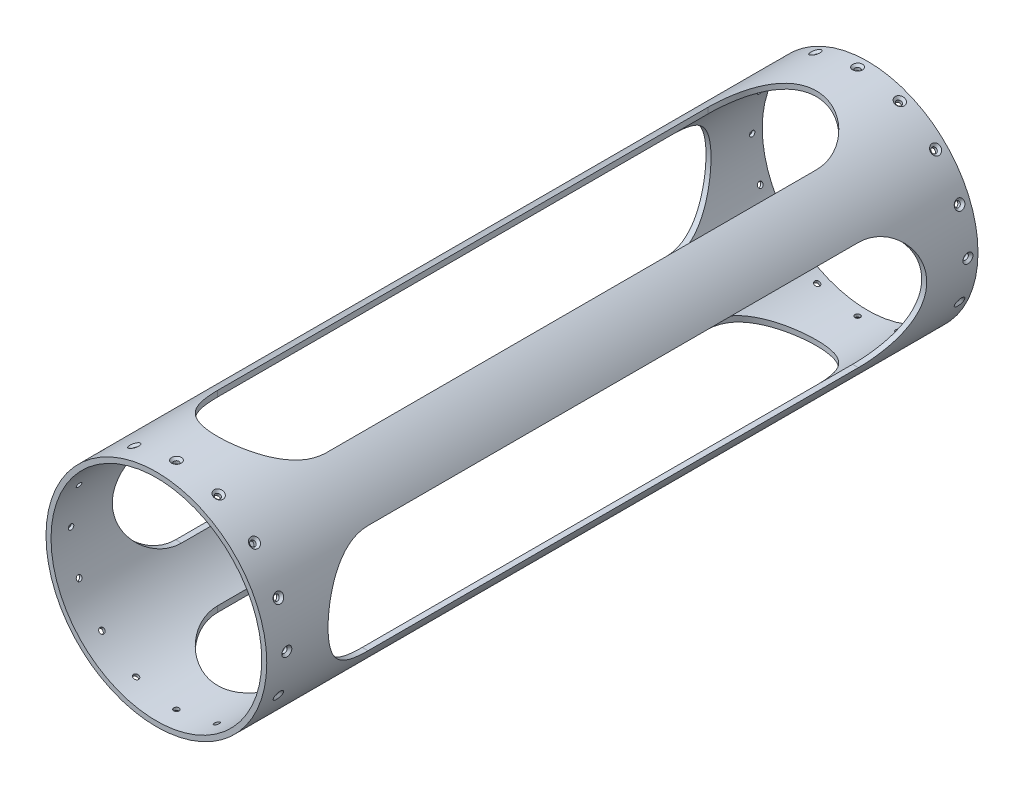
SolidWorks part; units mm, degrees
material "6061-T6 (SS)"
ref_plane "Front Plane" through (0, 0, 0) normal (0, 0, 1) x (1, 0, 0)
ref_plane "Top Plane" through (0, 0, 0) normal (0, 1, 0) x (1, 0, 0)
ref_plane "Right Plane" through (0, 0, 0) normal (1, 0, 0) x (0, 0, -1)
sketch "Sketch1" plane through (0, 0, 0) normal (0, 0, 1) x (1, 0, 0)
  circle A0 centre (0, 0) radius 66.675
  circle A1 centre (0, 0) radius 69.85
extrude "Extrude1" add sketch "Sketch1" along normal blind 228.2063
ref_plane "Plane2" through (0, 0, 215.5063) normal (0, 0, 1) x (1, 0, 0)
sketch "Sketch2" plane through (0, 0, 215.5063) normal (0, 0, 1) x (1, 0, 0)
  circle A0 centre (0, 0) radius 69.85 construction
  point P0 (0, -69.85)
ref_plane "Plane3" through (0, -69.85, 215.5063) normal (0, -1, 0) x (1, 0, 0)
hole_wizard "CSK for M3 Flat Head Machine Screw1" positions "Sketch4" profile "Sketch3" countersink size "M3" standard "Ansi Metric" end condition through all
sketch "Sketch4" plane through (0, -69.85, 215.5063) normal (0, -1, 0) x (1, 0, 0)
  point P1 (0, 0)
sketch "Sketch3" plane through (0, -69.85, 215.5063) normal (1, 0, 0) x (0, 0, -1)
  line L0 (0, 0) -> (0, 161.1134)
  line L1 (0, 161.1134) -> (1.7, 161.1134)
  line L2 (1.7, 161.1134) -> (1.7, 1.45)
  line L3 (1.7, 1.45) -> (3.15, 0)
  line L5 (3.15, 0) -> (0, 0)
  line L6 (-1.7, 1.45) -> (-3.15, 0) construction
  line L11 (0, -6.35) -> (0, 107.95) construction
  dimension "Thru Hole Dia." = 3.4
  dimension "Thru Hole Depth" = 161.1134
  dimension "Near C'Sink Dia." = 6.3
  dimension "Near C'Sink Angle" = 90
sketch "Sketch5" plane through (0, 0, 0) normal (0, 1, 0) x (1, 0, 0)
  line L0 (0, 0) -> (34.29, 0)
  line L1 (69.85, 0) -> (-69.85, 0) construction
  line L2 (0, 0) -> (-34.29, 0)
  line L3 (66.675, 0) -> (-66.675, 0) construction
  line L4 (-34.29, 0) -> (-34.29, -155.1392)
  line L5 (34.29, 0) -> (34.29, -155.1392)
  line L6 (-34.29, -155.1392) -> (34.29, -155.1392) construction
  arc A0 (-34.29, -155.1392) -> (34.29, -155.1392) centre (0, -155.1392) ccw
  dimension "D1" = 155.1392
extrude "Extrude2" cut sketch "Sketch5" against normal through all and the other way through all
pattern_circular "CirPattern2" count 4 over 360 about axis through (0, 0, 228.2063) along (0, 0, -1) of "Extrude2"
pattern_circular "CirPattern1" count 16 over 360 about axis through (0, 0, 228.2063) along (0, 0, -1) of "CSK for M3 Flat Head Machine Screw1"
mirror "Mirror1" about plane through (0, 0, 0) normal (0, 0, 1) of "CirPattern2", "Extrude2", "Extrude1", "CirPattern1", "CSK for M3 Flat Head Machine Screw1"
sketch "Sketch6" plane through (0, 0, -228.2063) normal (0, 0, -1) x (-1, 0, 0)
  circle A0 centre (0, 0) radius 69.85
extrude "Extrude3" cut sketch "Sketch6" against normal blind 6.35
